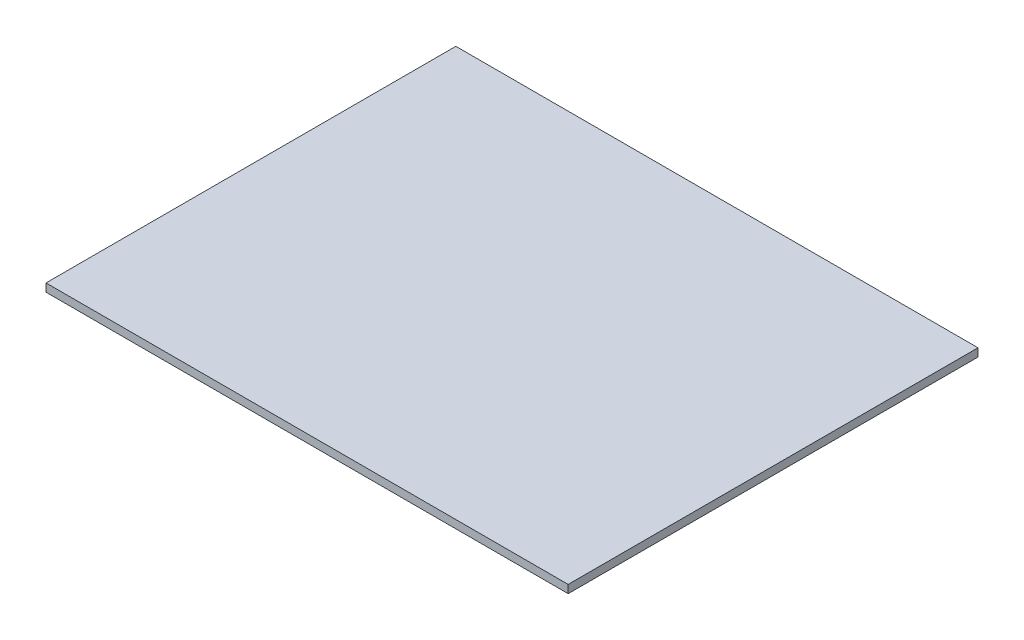
SolidWorks part; units mm, degrees
ref_plane "Front Plane" through (0, 0, 0) normal (0, 0, 1) x (1, 0, 0)
ref_plane "Top Plane" through (0, 0, 0) normal (0, 1, 0) x (1, 0, 0)
ref_plane "Right Plane" through (0, 0, 0) normal (1, 0, 0) x (0, 0, -1)
sketch "Sketch1" plane through (0, 0, 0) normal (0, 1, 0) x (1, 0, 0)
  line L1 (32.425, -25.45) -> (-32.425, -25.45)
  line L2 (32.425, -25.45) -> (32.425, 25.45)
  line L3 (32.425, 25.45) -> (-32.425, 25.45)
  line L4 (-32.425, -25.45) -> (-32.425, 25.45)
  line L5 (32.425, -25.45) -> (-32.425, 25.45) construction
  line L6 (32.425, 25.45) -> (-32.425, -25.45) construction
  point P0 (0, 0)
extrude "Boss-Extrude1" add sketch "Sketch1" along normal blind 1
